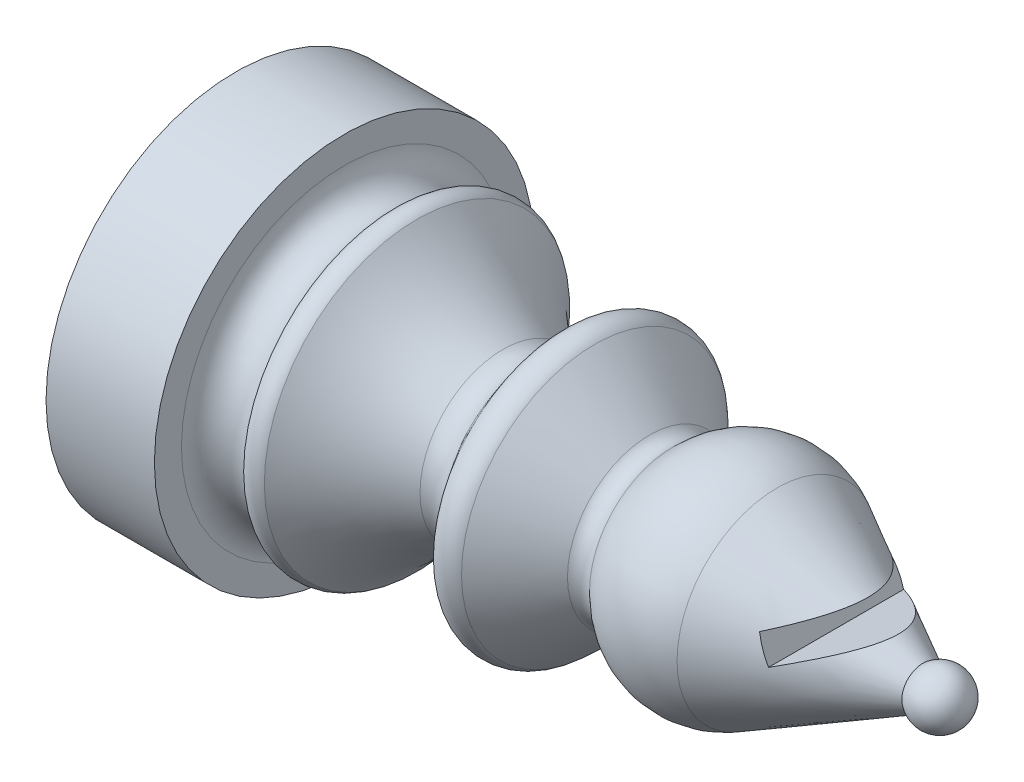
SolidWorks part; units mm, degrees
material "Latão"
ref_plane "Plano frontal" through (0, 0, 0) normal (0, 0, 1) x (1, 0, 0)
ref_plane "Plano superior" through (0, 0, 0) normal (0, 1, 0) x (1, 0, 0)
ref_plane "Plano direito" through (0, 0, 0) normal (1, 0, 0) x (0, 0, -1)
sketch "Esboço1" plane through (0, 0, 0) normal (0, 0, 1) x (1, 0, 0)
  line L0 (0, 0) -> (25, 0) construction
  line L1 (0, 0) -> (0, 6)
  line L2 (0, 6) -> (2, 6)
  line L3 (9.0265, 3.3256) -> (10.1214, 4.808)
  line L4 (11.2525, 4.9131) -> (13.2789, 3.0277)
  line L5 (17.9872, 3.69) -> (23.3737, 0.7796)
  line L6 (0, 0) -> (25, 0)
  arc A0 (2, 6) -> (3.9311, 5.6351) centre (3, 6) ccw
  arc A1 (3.9311, 5.6351) -> (4.6934, 5.6351) centre (4.3122, 5.1717) cw
  arc A2 (4.6934, 5.6351) -> (7.868, 3.0599) centre (12.7062, 12.2684) ccw
  arc A3 (10.1214, 4.808) -> (11.2525, 4.9131) centre (10.7338, 4.3556) cw
  arc A4 (14.1263, 3.0577) -> (17.9872, 3.69) centre (16.466, 0.8746) cw
  arc A5 (23.3737, 0.7796) -> (25, 0) centre (24, 0) cw
  arc A6 (13.2789, 3.0277) -> (14.1263, 3.0577) centre (13.6876, 3.467) ccw
  arc A7 (7.868, 3.0599) -> (9.0265, 3.3256) centre (8.2924, 3.8677) ccw
  dimension "D4" = 0.6
  dimension "D6" = 1
  dimension "D7" = 0.6
  dimension "D8" = 10.4022
  dimension "D12" = 3.2
  dimension "D14" = 1
  dimension "D1" = 25
  dimension "D2" = 6
  dimension "D3" = 2
  dimension "D15" = 1.9311
  dimension "D16" = 0.7623
  dimension "D23" = 3.8608
revolve "Revolução1" add sketch "Esboço1" angle 360 about L0
sketch "Esboço3" plane through (0, 0, 0) normal (0, 0, 1) x (1, 0, 0)
  line L0 (23.0229, 2.581) -> (19.7796, 1.2105)
  line L1 (19.7796, 1.2105) -> (20.1688, 0.2894)
  line L2 (20.1688, 0.2894) -> (23.4121, 1.6598)
  line L3 (23.4121, 1.6598) -> (23.0229, 2.581)
  dimension "D1" = 1
extrude "Corte-extrusão2" cut sketch "Esboço3" against normal mid plane 10
chamfer "Chanfro1" distance 0.25 angle 45 1 edges at (0, 0, 6)
sketch "Sketch1" plane through (0, 0, 0) normal (-1, 0, 0) x (0, 0, 1)
  circle A0 centre (0, 0) radius 7
  dimension "D1" = 14
extrude "Boss-Extrude1" add sketch "Sketch1" against normal blind 2
extrude "Boss-Extrude2" add sketch "Sketch1<2>" along normal blind 2
sketch "Sketch1<2>" plane through (0, 0, 0) normal (-1, 0, 0) x (0, 0, 1) same geometry as "Sketch1"
sketch "Sketch2" plane through (-2, 0, 0) normal (-1, 0, 0) x (0, 0, 1)
  circle A0 centre (0, 0) radius 6.05
  dimension "D1" = 12.1
extrude "Cut-Extrude1" cut sketch "Sketch2" against normal blind 3.2
